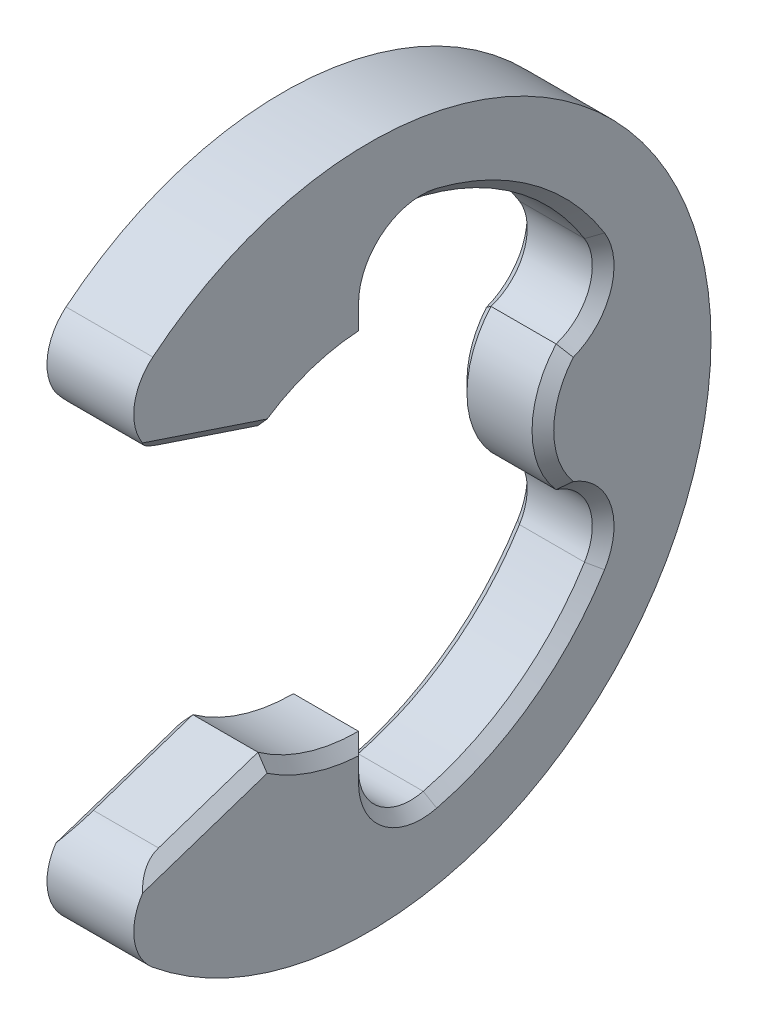
SolidWorks part; units mm, degrees
note: '?' marks a value the reader was unsure of.
ref_plane "Front" through (0, 0, 0) normal (0, 0, 1) x (1, 0, 0)
ref_plane "Top" through (0, 0, 0) normal (0, 1, 0) x (1, 0, 0)
ref_plane "Right" through (0, 0, 0) normal (1, 0, 0) x (0, 0, -1)
sketch "Sketch2" plane through (0, 0, 0) normal (1, 0, 0) x (0, 0, -1)
  line L0 (-2.3178, 3.26) -> (-2.3178, -3.26) construction
  circle A0 centre (0, 0) radius 7.875 construction
  circle A1 centre (0, 0) radius 4 construction
  dimension "Ring OD" = 15.75
  dimension "Ring Gap Width" = 6.52
sketch "Sketch3" plane through (0, 0, 0) normal (0, 1, 0) x (1, 0, 0)
  line L0 (1, 7.875) -> (-1, 7.875) construction
  line L1 (-0.525, -5.5125) -> (0.525, -5.5125) construction
  line L2 (-0.525, -5.5125) -> (-0.525, -5.8625) construction
  line L3 (0, -7.875) -> (0, 7.875) construction
  line L4 (0, -7.875) -> (0, 7.875) construction
  line L5 (0.525, -5.8625) -> (-0.525, -5.8625)
  point P4 (0, -5.5125)
  point P6 (0, 7.875)
  point P13 (0, -5.8625)
  dimension "D1" = 4.725
  dimension "Ring Thickness" = 2
  dimension "D2" = 0.35
sketch "Sketch1" plane through (0, 0, 0) normal (1, 0, 0) x (0, 0, -1)
  line L0 (-6.3811, -4.6149) -> (-2.3178, -3.26)
  line L1 (-6.3811, 4.6149) -> (-2.3178, 3.26)
  line L2 (0, -4) -> (0, -6.129)
  line L3 (0, 4) -> (0, 6.129)
  line L4 (3.8105, -1.2166) -> (5.8387, -1.8641)
  line L5 (3.8105, 1.2166) -> (5.8387, 1.8641)
  line L6 (0, 0) -> (-1.625, 0) construction
  line L7 (3.8105, 1.2166) -> (3.8105, -1.2166) construction
  line L8 (-2.3178, 3.26) -> (0, 4) construction
  line L9 (-2.3178, -3.26) -> (0, -4) construction
  line L10 (-2.3178, 3.26) -> (-2.3178, -3.26) construction
  circle A1 centre (0, 0) radius 7.875 construction
  circle A2 centre (0, 0) radius 4 construction
  arc A3 (-6.3811, -4.6149) -> (-6.3811, 4.6149) centre (0, 0) ccw
  arc A4 (-2.3178, 3.26) -> (0, 4) centre (0, 0) cw
  arc A5 (-2.3178, -3.26) -> (0, -4) centre (0, 0) ccw
  arc A6 (3.8105, 1.2166) -> (3.8105, -1.2166) centre (0, 0) cw
  arc A7 (0, -6.129) -> (5.8387, -1.8641) centre (0, 0) ccw
  arc A8 (5.8387, 1.8641) -> (0, 6.129) centre (0, 0) ccw
  circle A9 centre (0, 0) radius 4 construction
  point P12 (3.8105, 0)
  dimension "D1" = 6.129
  dimension "D2" = 4.7189
extrude "Extrude1" add sketch "Sketch1" along normal mid plane 2
fillet "Fillet1" radius 1.2 6 edges at (0, -6.129, 0) (0, 6.129, 0) (0, -4.6149, 6.3811) (0, 4.6149, 6.3811) (0, -1.8641, -5.8387) (0, 1.8641, -5.8387)
sketch "Sketch4" plane through (0, 0, 0) normal (1, 0, 0) x (0, 0, -1)
  line L1 (0, 4.7807) -> (0, -4.7807)
  arc A1 (4.5543, -1.454) -> (4.5543, 1.454) centre (6.1843, 0) cw
  arc A2 (3.8105, -1.2166) -> (3.8105, 1.2166) centre (0, 0) ccw construction
  arc A7 (1.4921, 5.9446) -> (0, 4.7807) centre (1.2, 4.7807) ccw construction
  arc A8 (5.2092, 3.2294) -> (1.4921, 5.9446) centre (0, 0) ccw construction
  arc A9 (4.5543, 1.454) -> (5.2092, 3.2294) centre (4.1893, 2.5972) ccw construction
  arc A10 (5.2092, -3.2294) -> (4.5543, -1.454) centre (4.1893, -2.5972) ccw construction
  arc A11 (1.4921, -5.9446) -> (5.2092, -3.2294) centre (0, 0) ccw construction
  arc A12 (0, -4.7807) -> (1.4921, -5.9446) centre (1.2, -4.7807) ccw construction
  arc A13 (1.4921, 5.9446) -> (0, 4.7807) centre (1.2, 4.7807) ccw
  arc A14 (5.2092, 3.2294) -> (1.4921, 5.9446) centre (0, 0) ccw
  arc A15 (4.5543, 1.454) -> (5.2092, 3.2294) centre (4.1893, 2.5972) ccw
  arc A16 (5.2092, -3.2294) -> (4.5543, -1.454) centre (4.1893, -2.5972) ccw
  arc A17 (1.4921, -5.9446) -> (5.2092, -3.2294) centre (0, 0) ccw
  arc A18 (0, -4.7807) -> (1.4921, -5.9446) centre (1.2, -4.7807) ccw
extrude "Cut-Extrude1" cut sketch "Sketch4" against normal through all both and the other way through all
ref_plane "Contact Plane 1" through (1, 0, 0) normal (1, 0, 0) x (0, 0, -1)
ref_plane "Contact Plane 2" through (-1, 0, 0) normal (-1, 0, 0) x (0, 0, 1)
ref_axis "Center Axis 1" through (6.2343, 0, 0) along (-1, 0, 0)?
chamfer "Chamfer1" distance 0.25 angle 45 25 edges at (1, 3.6422, 3.4642) (1, 3.8105, 1.2166) (1, 5.7269, -0.462) (1, 4.9492, -3.6153) (1, 2.1818, -5.3151) (1, 0, -4) (1, -2.1818, -5.3151) (1, -4.9492, -3.6153) (1, -5.7269, -0.462) (1, -4.3904, 0) (1, -3.8105, 1.2166) (1, -3.6422, 3.4642) (-1, 3.6422, 3.4642) (-1, 3.8105, 1.2166) (-1, 4.3904, 0) (-1, 5.7269, -0.462) (-1, 4.9492, -3.6153) (-1, 2.1818, -5.3151) (-1, 0, -4) (-1, -2.1818, -5.3151) (-1, -4.9492, -3.6153) (-1, -5.7269, -0.462) (-1, -4.3904, 0) (-1, -3.8105, 1.2166) (-1, -3.6422, 3.4642)
equation "\"D1@Fillet1\" = \"Ring Thickness@Sketch3\" * .6"
equation "\"D1@Sketch1\" =  ( \"Ring OD@Sketch2\" + \"For Groove Diameter@Sketch2\" )  / 3.875"
equation "\"D1@Sketch3\"=\"Ring OD@Sketch2\"*.3"
equation "\"D2@Extrude1\"=\"Ring Thickness@Sketch3\""
equation "\"D2@Sketch3\" = \"For Groove Width@Sketch3\" / 3"
